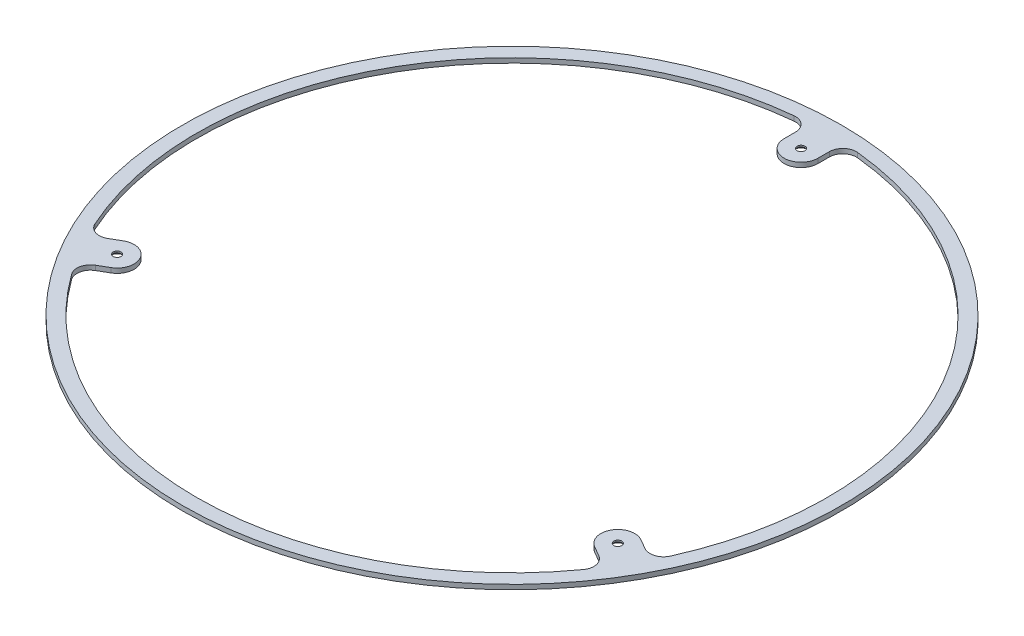
SolidWorks part; units mm, degrees
ref_plane "Front Plane" through (0, 0, 0) normal (0, 0, 1) x (1, 0, 0)
ref_plane "Top Plane" through (0, 0, 0) normal (0, 1, 0) x (1, 0, 0)
ref_plane "Right Plane" through (0, 0, 0) normal (1, 0, 0) x (0, 0, -1)
sketch "Sketch1" plane through (0, 0, 0) normal (0, 1, 0) x (1, 0, 0)
  circle A0 centre (0, 0) radius 146
  circle A1 centre (0, 0) radius 139.75
  dimension "D1" = 292
  dimension "D2" = 279.5
extrude "Boss-Extrude1" add sketch "Sketch1" along normal blind 2.07
sketch "Sketch2" plane through (0, 0, 0) normal (0, 1, 0) x (1, 0, 0)
  line L0 (-7.5, 128.0585) -> (-7.5, 139.5486)
  line L1 (7.5, 128.0585) -> (7.5, 139.5486)
  circle A0 centre (0, 0) radius 128.0585 construction
  circle A1 centre (0, 128.0585) radius 1.75
  arc A2 (-7.5, 128.0585) -> (7.5, 128.0585) centre (0, 128.0585) ccw
  circle A5 centre (0, 0) radius 139.75 construction
  arc A6 (7.5, 139.5486) -> (-7.5, 139.5486) centre (0, 0) ccw
  point P3 (0, 128.0585)
  dimension "D1" = 256.117
  dimension "D2" = 3.5
  dimension "D3" = 15
extrude "Boss-Extrude2" add sketch "Sketch2" along normal up to surface (2.07 mm away) up to face at (0, 2.07, 146)
sketch "Sketch4" plane through (0, 0, 0) normal (0, -1, 0) x (1, 0, 0)
  circle A0 centre (0, -128.0585) radius 1.75 construction
  circle A1 centre (0, -128.0585) radius 1.75
hole_wizard "CSK for M3 Countersunk Flat Head Screw1" positions "3DSketch1" profile "Sketch5" countersink size "M3" standard "DIN" end condition through all
sketch3d "3DSketch1"
  point P0 (0, 0, -128.0585)
sketch "Sketch5" plane through (0, 0, -128.0585) normal (1, 0, 0) x (0, 0, -1)
  line L0 (0, 0) -> (0, 2.07)
  line L1 (0, 2.07) -> (1.7, 2.07)
  line L2 (1.7, 2.07) -> (1.7, 1.45)
  line L3 (1.7, 1.45) -> (3.15, 0)
  line L5 (3.15, 0) -> (0, 0)
  line L6 (-1.7, 1.45) -> (-3.15, 0) construction
  line L11 (0, -6.35) -> (0, 107.95) construction
  dimension "Thru Hole Dia." = 3.4
  dimension "Thru Hole Depth" = 2.07
  dimension "Near C'Sink Dia." = 6.3
  dimension "Near C'Sink Angle" = 90
fillet "Fillet1" radius 6 2 edges at (-7.5, 1.035, -139.5486) (7.5, 1.035, -139.5486)
pattern_circular "CirPattern1" count 3 over 360 about axis through (0, 0, 0) along (0, 1, 0) of "Boss-Extrude2", "CSK for M3 Countersunk Flat Head Screw1", "Fillet1"
